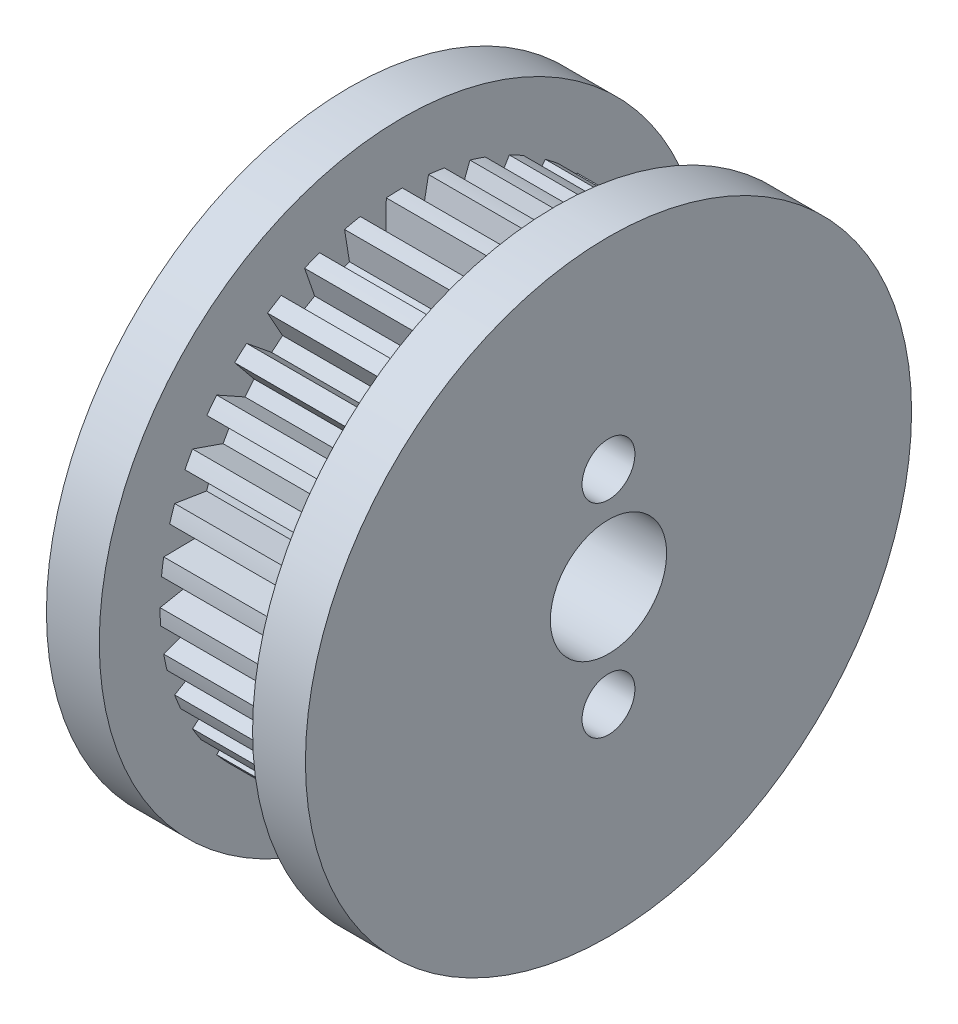
SolidWorks part; units mm, degrees
ref_plane "Front Plane" through (0, 0, 0) normal (0, 0, 1) x (1, 0, 0)
ref_plane "Top Plane" through (0, 0, 0) normal (0, 1, 0) x (1, 0, 0)
ref_plane "Right Plane" through (0, 0, 0) normal (1, 0, 0) x (0, 0, -1)
sketch "Sketch2" plane through (0, 0, 0) normal (0, 0, 1) x (1, 0, 0)
  line L0 (-6.223, 2.794) -> (6.223, 2.794)
  line L1 (6.223, 2.794) -> (6.223, 14.5644)
  line L2 (6.223, 14.5644) -> (3.683, 14.5644)
  line L3 (-3.683, 11.6434) -> (3.683, 11.6434)
  line L4 (3.683, 11.6434) -> (3.683, 14.5644)
  line L5 (-3.683, 11.6434) -> (-3.683, 14.5644)
  line L6 (-3.683, 14.5644) -> (-6.223, 14.5644)
  line L8 (-6.223, 2.794) -> (-6.223, 14.5644)
  line L10 (-20.1478, 0) -> (36.4859, 0) construction
  point P8 (0, 11.6434)
  dimension "D1" = 2.794
  dimension "D2" = 7.366
  dimension "D3" = 11.6434
  dimension "D4" = 2.921
  dimension "D5" = 2.54
ref_axis "Axis1" through (-20.1478, 0, 0) along (1, 0, 0)
revolve "Revolve1" add sketch "Sketch2" angle 360 about L10
sketch "Sketch3" plane through (3.683, 0, 0) normal (-1, 0, 0) x (0, 0, 1)
  line L0 (-1.27, 11.6434) -> (-0.9779, 10.1194)
  line L1 (-0.9779, 10.1194) -> (-0.2921, 10.1194)
  line L2 (-0.2921, 10.1194) -> (0, 11.6434)
  line L3 (0, 11.6434) -> (-1.27, 11.6434)
  circle A0 centre (0, 0) radius 11.6434 construction
  point P6 (-0.635, 11.6434)
  point P7 (-0.635, 10.1194)
  dimension "D3" = 1.524
  dimension "D1" = 1.27
  dimension "D2" = 0.6858
extrude "Cut-Extrude1" cut sketch "Sketch3" along normal up to surface (7.366 mm away) up to face at (-3.683, 0, 14.5644)
pattern_circular "CirPattern1" count 36 over 360 about axis through (3.683, 0, 0) along (-1, 0, 0) of "Cut-Extrude1"
sketch "Sketch5" plane through (-6.223, 0, 0) normal (-1, 0, 0) x (0, 0, 1)
  circle A0 centre (0, 4.8895) radius 1.27
  circle A1 centre (0, -4.8895) radius 1.27
  dimension "D1" = 2.54
  dimension "D2" = 2.54
  dimension "D4" = 4.8895
  dimension "D3" = 9.779
extrude "Cut-Extrude2" cut sketch "Sketch5" against normal blind 22.86
